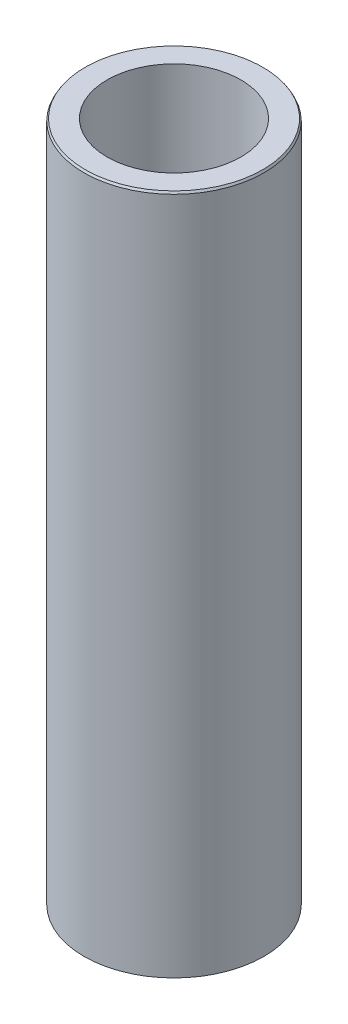
SolidWorks part; units mm, degrees
ref_plane "Front Plane" through (0, 0, 0) normal (0, 0, 1) x (1, 0, 0)
ref_plane "Top Plane" through (0, 0, 0) normal (0, 1, 0) x (1, 0, 0)
ref_plane "Right Plane" through (0, 0, 0) normal (1, 0, 0) x (0, 0, -1)
sketch "Sketch1" plane through (0, 0, 0) normal (0, 1, 0) x (1, 0, 0)
  circle A0 centre (0, 0) radius 37.5
  dimension "SHAFT_OD" = 75
extrude "Boss-Extrude1" add sketch "Sketch1" along normal blind 284.1305
sketch "Sketch2" plane through (0, 0, 0) normal (0, 1, 0) x (1, 0, 0)
  circle A0 centre (0, 0) radius 27.8699
  dimension "BORE_D" = 55.7399
extrude "Cut-Extrude1" cut sketch "Sketch2" along normal through all
chamfer "Chamfer1" distance 0.871 angle 30 2 edges at (0, 284.1305, 37.5) (0, 0, 37.5) first distance on face at (0, 284.1305, 37.5) first distance on face at (0, 0, 27.8699)
